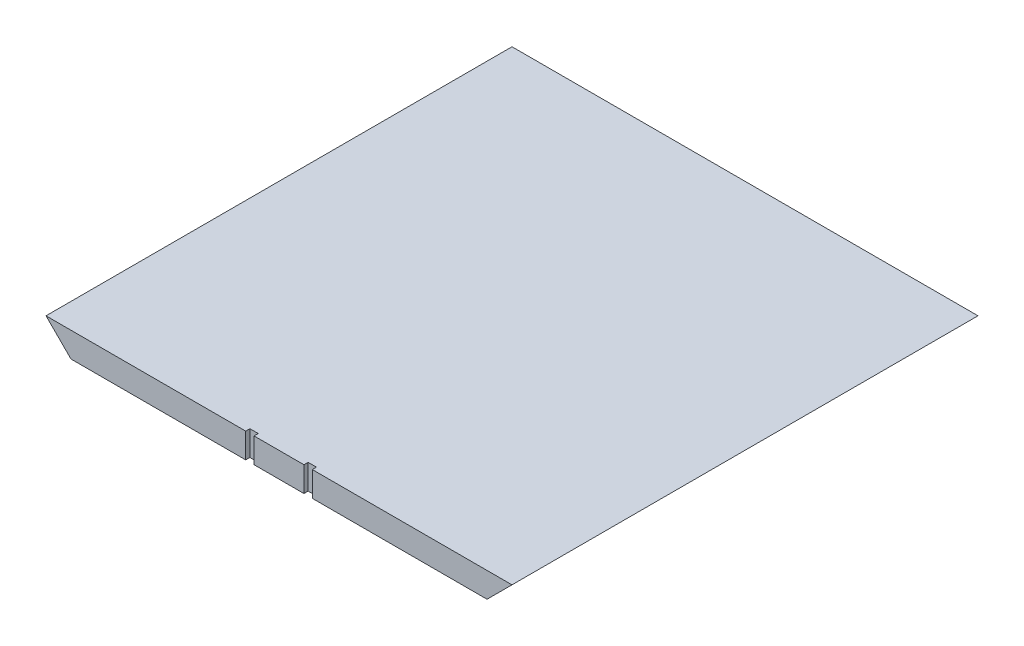
SolidWorks part; units mm, degrees
ref_plane "Front Plane" through (0, 0, 0) normal (0, 0, 1) x (1, 0, 0)
ref_plane "Top Plane" through (0, 0, 0) normal (0, 1, 0) x (1, 0, 0)
ref_plane "Right Plane" through (0, 0, 0) normal (1, 0, 0) x (0, 0, -1)
sketch "Sketch1" plane through (0, 0, 0) normal (0, 1, 0) x (1, 0, 0)
  line L1 (177.8, 177.8) -> (-177.8, 177.8)
  line L2 (177.8, 177.8) -> (177.8, -177.8)
  line L3 (177.8, -177.8) -> (-177.8, -177.8)
  line L4 (-177.8, 177.8) -> (-177.8, -177.8)
  line L5 (177.8, 177.8) -> (-177.8, -177.8) construction
  line L6 (177.8, -177.8) -> (-177.8, 177.8) construction
  point P0 (0, 0)
  dimension "D1" = 355.6
  dimension "D2" = 355.6
extrude "Boss-Extrude1" add sketch "Sketch1" along normal mid plane 19.05
chamfer "Chamfer1" distance 19.05 angle 45 2 edges at (177.8, -9.525, 0) (-177.8, -9.525, 0)
sketch "Sketch2" plane through (0, 0, 177.8) normal (0, 0, 1) x (1, 0, 0)
  line L0 (19.05, 9.525) -> (19.05, -219.075) construction
  line L1 (25.4, 9.525) -> (25.4, -219.075) construction
  line L2 (19.05, 9.525) -> (25.4, 9.525) construction
  line L3 (-19.05, 9.525) -> (-19.05, -219.075) construction
  line L4 (-25.4, 9.525) -> (-19.05, 9.525) construction
  line L5 (-25.4, 9.525) -> (-25.4, -219.075) construction
  line L6 (19.05, 9.525) -> (19.05, -9.525)
  line L7 (25.4, 9.525) -> (25.4, -9.525)
  line L8 (19.05, 9.525) -> (25.4, 9.525)
  line L9 (-19.05, 9.525) -> (-19.05, -9.525)
  line L10 (-25.4, 9.525) -> (-19.05, 9.525)
  line L11 (-25.4, 9.525) -> (-25.4, -9.525)
  line L12 (-25.4, -9.525) -> (-19.05, -9.525)
  line L13 (-158.75, -9.525) -> (158.75, -9.525) construction
  line L14 (25.4, -9.525) -> (19.05, -9.525)
extrude "Cut-Extrude1" cut sketch "Sketch2" against normal blind 3.175
